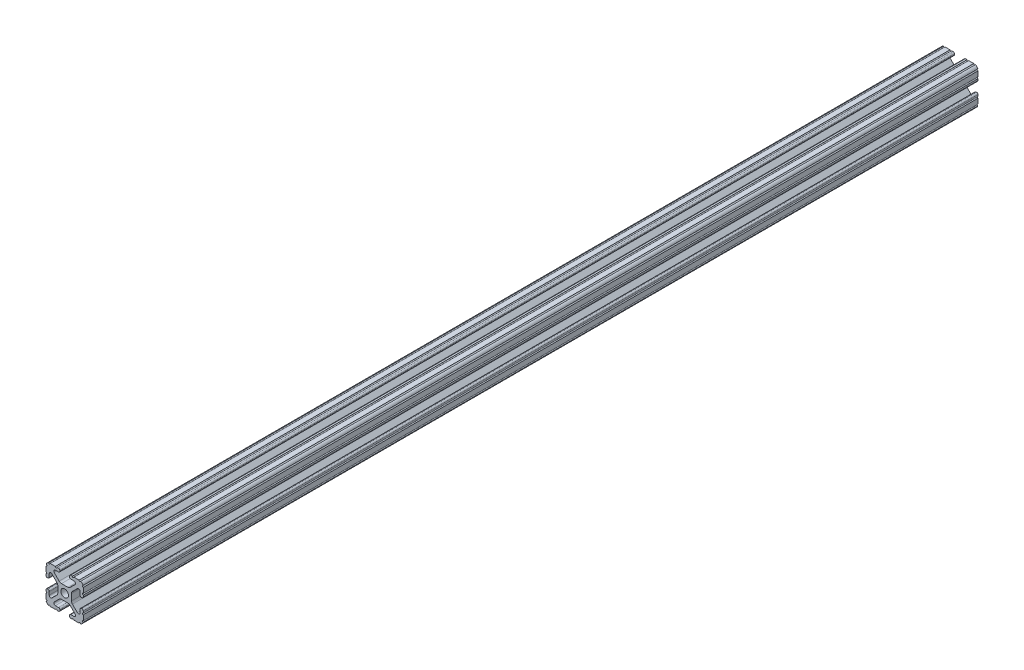
SolidWorks part; units mm, degrees
ref_plane "Front Plane" through (0, 0, 0) normal (0, 0, 1) x (1, 0, 0)
ref_plane "Top Plane" through (0, 0, 0) normal (0, 1, 0) x (1, 0, 0)
ref_plane "Right Plane" through (0, 0, 0) normal (1, 0, 0) x (0, 0, -1)
sketch "Sketch2" plane through (0, 0, 0) normal (0, 0, 1) x (1, 0, 0)
  line L0 (0, 12.7) -> (0, -12.7) construction
  line L1 (-12.7, 0) -> (12.7, 0) construction
  line L2 (3.2512, -12.7) -> (12.7, -12.7)
  line L3 (12.7, -12.7) -> (12.7, -3.2512)
  line L4 (3.2512, -12.7) -> (3.2512, -10.4902)
  line L5 (3.2512, -10.4902) -> (8.9276, -10.4902)
  line L6 (8.9276, -10.4902) -> (3.0856, -4.6482)
  line L7 (0, 0) -> (12.7, -12.7) construction
  line L8 (12.7, -3.2512) -> (10.4902, -3.2512)
  line L9 (10.4902, -3.2512) -> (10.4902, -8.9276)
  line L10 (10.4902, -8.9276) -> (4.6482, -3.0856)
  circle A0 centre (0, 0) radius 2.6035
  arc A1 (6.3485, -10.4902) -> (7.1039, -8.6665) centre (6.3485, -9.4219) ccw construction
  point P8 (0, -4.6482)
  dimension "Center Hole Diameter" = 5.207
  dimension "Rail Height" = 25.4
  dimension "Rail Width" = 25.4
  dimension "T-Slot Width" = 6.5024
  dimension "Slot Inner Width" = 14.8336
  dimension "Thickness" = 2.2098
  dimension "Slot Depth" = 5.842
  dimension "D1" = 2.2098
sketch "Sketch3" plane through (0, 0, 0) normal (1, 0, 0) x (0, 0, -1)
  line L0 (-304.8, -12.7) -> (304.8, -12.7) construction
  line L1 (-279.4, 0) -> (279.4, 0) construction
  dimension "Length" = 609.6
  dimension "D1" = 25.4
sketch "Sketch4" plane through (0, 0, 0) normal (0, 0, 1) x (1, 0, 0)
  line L0 (4.1904, -12.7) -> (10.1173, -12.7)
  line L1 (3.2512, -12.7) -> (12.7, -12.7) construction
  line L2 (3.2512, -12.7) -> (3.2512, -10.4902) construction
  line L3 (3.2512, -10.4902) -> (8.9276, -10.4902) construction
  line L4 (3.2512, -11.4294) -> (3.2512, -11.7608)
  line L5 (4.1904, -10.4902) -> (6.3485, -10.4902)
  line L6 (0, -4.6482) -> (2.164, -4.6482)
  line L7 (8.9276, -10.4902) -> (3.0856, -4.6482) construction
  line L8 (3.7373, -5.2999) -> (7.1039, -8.6665)
  line L9 (12.7, -12.7) -> (12.7, -3.2512) construction
  line L10 (10.4902, -8.9276) -> (4.6482, -3.0856) construction
  line L11 (10.4902, -3.2512) -> (10.4902, -8.9276) construction
  line L12 (10.4902, -6.3485) -> (10.4902, -4.1904)
  line L13 (12.7, -3.2512) -> (10.4902, -3.2512) construction
  line L14 (11.4294, -3.2512) -> (11.7608, -3.2512)
  line L15 (12.7, -4.1904) -> (12.7, -10.1173)
  line L16 (8.6665, -7.1039) -> (5.2999, -3.7373)
  line L17 (4.6482, 0) -> (4.6482, -2.164)
  line L18 (-12.7, 0) -> (12.7, 0) construction
  line L19 (0, -4.6482) -> (0, -2.6035)
  line L20 (0, 12.7) -> (0, -12.7) construction
  line L21 (4.6482, 0) -> (2.6035, 0)
  arc A0 (3.2512, -11.7608) -> (4.1904, -12.7) centre (4.1904, -11.7608) ccw
  arc A2 (3.2512, -11.4294) -> (4.1904, -10.4902) centre (4.1904, -11.4294) cw
  arc A3 (6.3485, -10.4902) -> (7.1039, -8.6665) centre (6.3485, -9.4219) ccw
  arc A4 (2.164, -4.6482) -> (3.7373, -5.2999) centre (2.164, -6.8732) cw
  arc A5 (10.1173, -12.7) -> (12.7, -10.1173) centre (10.1173, -10.1173) ccw
  arc A6 (8.6665, -7.1039) -> (10.4902, -6.3485) centre (9.4219, -6.3485) ccw
  arc A7 (10.4902, -4.1904) -> (11.4294, -3.2512) centre (11.4294, -4.1904) cw
  arc A8 (11.7608, -3.2512) -> (12.7, -4.1904) centre (11.7608, -4.1904) cw
  arc A9 (5.2999, -3.7373) -> (4.6482, -2.164) centre (6.8732, -2.164) cw
  circle A10 centre (0, 0) radius 2.6035 construction
  arc A11 (0, -2.6035) -> (2.6035, 0) centre (0, 0) ccw
  dimension "D1" = 2.5827
  dimension "D2" = 2.225
  dimension "D3" = 0.9392
extrude "Boss-Extrude1" add sketch "Sketch4" along normal mid plane 609.6
sketch "Sketch5" plane through (0, 0, 0) normal (0, 0, 1) x (1, 0, 0)
  line L0 (3.2512, -12.7) -> (12.7, -12.7) construction
  line L1 (4.1904, -10.4902) -> (6.3485, -10.4902) construction
  line L3 (0, 0) -> (12.7, -12.7) construction
  line L4 (6.3485, -10.4902) -> (6.3485, -12.7) construction
  line L5 (8.9276, -10.4902) -> (3.0856, -4.6482) construction
  circle A0 centre (10.3562, -12.7) radius 0.5524
  circle A1 centre (5.796, -12.7) radius 0.5524
  circle A2 centre (12.7, -10.3562) radius 0.5524
  circle A3 centre (12.7, -5.796) radius 0.5524
  point P10 (5.2694, -10.4902)
  point P12 (9.4219, -6.3485)
  dimension "D1" = 1.1049
extrude "Cut-Extrude1" cut sketch "Sketch5" against normal through all both and the other way through all
mirror "Mirror1" about plane through (0, 0, 0) normal (1, 0, 0) of bodies 137 134
mirror "Mirror2" about plane through (0, 0, 0) normal (0, 1, 0) of bodies 135
equation "\"D1@Boss-Extrude1\"=\"Length@Sketch3\""
equation "\"D1@Sketch2\"=\"Thickness@Sketch2\""
equation "\"D2@Sketch4\"=\"Slot Inner Width@Sketch2\"*0.15"
equation "\"D1@Sketch4\"=\"D3@Sketch4\"*2.75"
equation "\"D3@Sketch4\"=\"Thickness@Sketch2\"*0.425"
equation "\"D1@Sketch5\"=\"Thickness@Sketch2\"*0.5"
